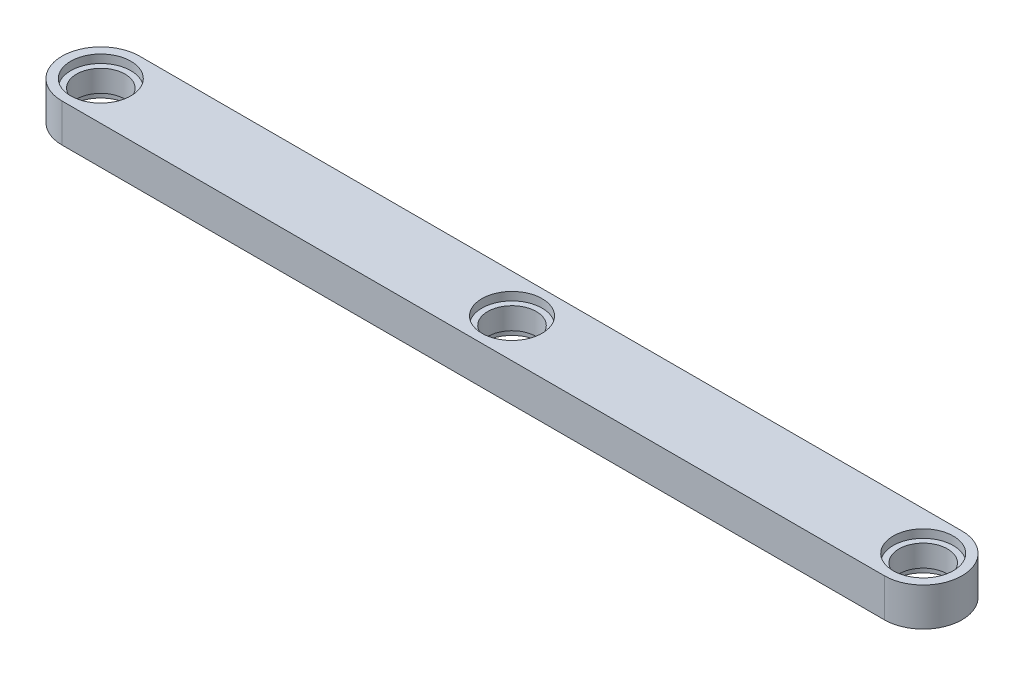
SolidWorks part; units mm, degrees
ref_plane "Front Plane" through (0, 0, 0) normal (0, 0, 1) x (1, 0, 0)
ref_plane "Top Plane" through (0, 0, 0) normal (0, 1, 0) x (1, 0, 0)
ref_plane "Right Plane" through (0, 0, 0) normal (1, 0, 0) x (0, 0, -1)
sketch "Croquis1" plane through (0, 0, 0) normal (0, 1, 0) x (1, 0, 0)
  line L0 (0, 0) -> (84.76, 0) construction
  line L1 (0, 4) -> (84.76, 4)
  line L2 (0, -4) -> (84.76, -4)
  circle A0 centre (0, 0) radius 3.1
  circle A1 centre (0, 0) radius 2.5
  circle A2 centre (84.76, 0) radius 3.1
  circle A3 centre (84.76, 0) radius 2.5
  arc A4 (0, 4) -> (0, -4) centre (0, 0) ccw
  arc A5 (84.76, -4) -> (84.76, 4) centre (84.76, 0) ccw
  circle A6 centre (42.38, 0) radius 2.5
  circle A7 centre (42.38, 0) radius 3.1
  point P7 (42.38, 0)
  dimension "D1" = 5
  dimension "D2" = 6.2
  dimension "D3" = 4
  dimension "D4" = 84.76
extrude "Saliente-Extruir1" add sketch "Croquis1" along normal blind 3.935 contours L2 A5 L1 A4 A0 A2 region at (42.38, 0, -3.9069)
extrude "Saliente-Extruir2" add sketch "Croquis1<3>" along normal offset from surface (2.235 mm away) 0.85 from offset 0.85 contours A1 A0 | A2 A3 | L0 A7 A6 | A7 L0 A6 region at (-3.0123, 0, 0) region at (84.76, 0, -3.0123) region at (42.38, 0, -3.0307) region at (39.58, 0, 0.0693) up to face at (42.38, 3.935, 3.1)
sketch "Croquis1<3>" plane through (0, 0, 0) normal (0, 1, 0) x (1, 0, 0) same geometry as "Croquis1"
equation "\"longitud\"= 84.76"
equation "\"D4@Croquis1\"=\"longitud\""
equation "\"ancho\"= 7.87"
equation "\"offset\"=0.85"
equation "\"D19@Saliente-Extruir2\"=\"offset\""
equation "\"D1@Saliente-Extruir2\"=\"offset\""
equation "\"D1@Saliente-Extruir1\"=\"ancho\"/2"
